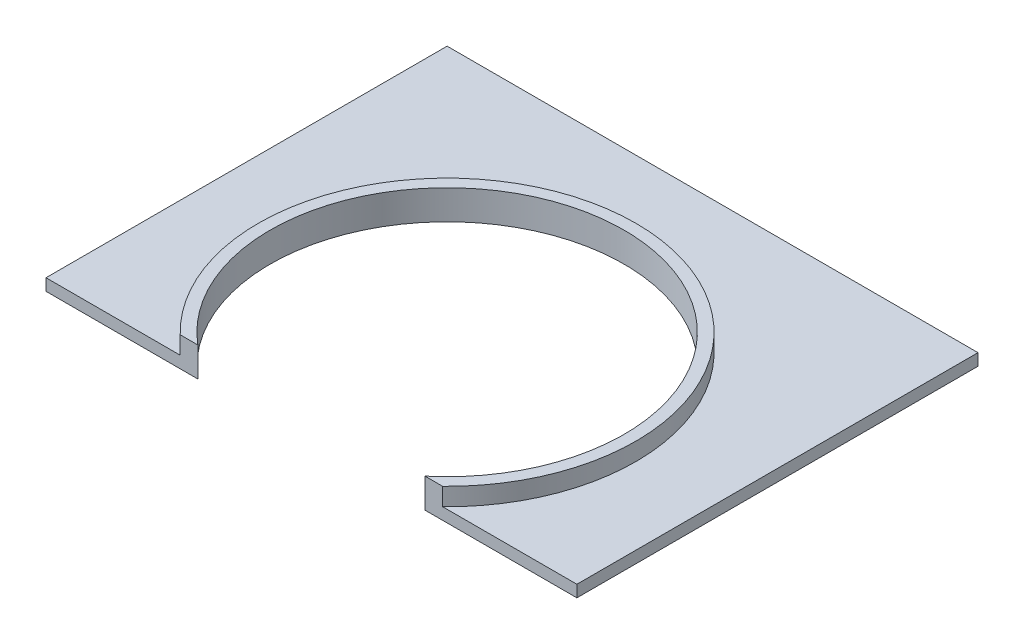
SolidWorks part; units mm, degrees
ref_plane "Alzado" through (0, 0, 0) normal (0, 0, 1) x (1, 0, 0)
ref_plane "Planta" through (0, 0, 0) normal (0, 1, 0) x (1, 0, 0)
ref_plane "Vista lateral" through (0, 0, 0) normal (1, 0, 0) x (0, 0, -1)
sketch "Croquis1" plane through (0, 0, 0) normal (0, 1, 0) x (1, 0, 0)
  line L1 (-45, 45) -> (45, 45)
  line L2 (-45, 45) -> (-45, -45)
  line L3 (-45, -45) -> (45, -45)
  line L4 (45, 45) -> (45, -45)
  line L5 (-45, 45) -> (45, -45) construction
  line L6 (-45, -45) -> (45, 45) construction
  circle A0 centre (0, 0) radius 30
  dimension "D1" = 60
  dimension "D2" = 90
  dimension "D3" = 90
extrude "Saliente-Extruir1" add sketch "Croquis1" along normal blind 2
sketch "Croquis2" plane through (0, 2, 0) normal (0, 1, 0) x (1, 0, 0)
  circle A0 centre (0, 0) radius 30 construction
  circle A1 centre (0, 0) radius 30
  circle A2 centre (0, 0) radius 32
  dimension "D1" = 2
extrude "Saliente-Extruir2" add sketch "Croquis2" along normal blind 3
sketch "Croquis3" plane through (0, 5, 0) normal (0, 1, 0) x (1, 0, 0)
  line L0 (-45, 45) -> (-45, -45) construction
  line L1 (-45, -45) -> (45, -45)
  line L2 (-45, -45) -> (-45, -23)
  line L3 (-45, -23) -> (45, -23)
  line L4 (45, -45) -> (45, -23)
  line L5 (45, -45) -> (45, 45) construction
  line L6 (-45, -45) -> (45, -45) construction
  dimension "D1" = 22
extrude "Cortar-Extruir1" cut sketch "Croquis3" against normal through all
